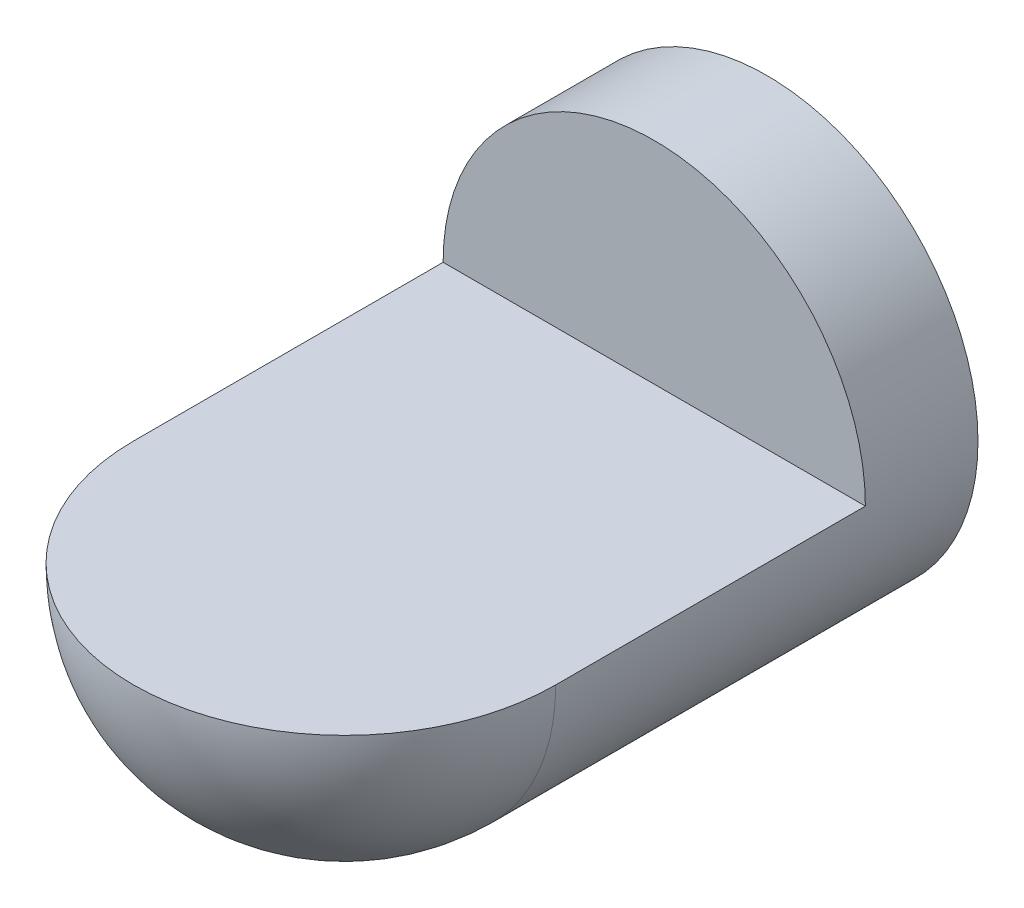
SolidWorks part; units mm, degrees
ref_plane "Front Plane" through (0, 0, 0) normal (0, 0, 1) x (1, 0, 0)
ref_plane "Top Plane" through (0, 0, 0) normal (0, 1, 0) x (1, 0, 0)
ref_plane "Right Plane" through (0, 0, 0) normal (1, 0, 0) x (0, 0, -1)
sketch "Sketch1" plane through (0, 0, 0) normal (1, 0, 0) x (0, 0, -1)
  line L0 (-146.9091, 0) -> (313.5945, 0) construction
  line L1 (150, 0) -> (-75, 0)
  line L2 (150, 0) -> (150, 75)
  line L3 (0, 75) -> (150, 75)
  arc A0 (-75, 0) -> (0, 75) centre (0, 0) cw
  dimension "D1" = 75
  dimension "D2" = 150
revolve "Revolve1" add sketch "Sketch1" angle 360 about L0
sketch "Sketch2" plane through (0, 0, 0) normal (1, 0, 0) x (0, 0, -1)
  line L0 (-88.0407, 0) -> (120.4455, 0) construction
  line L1 (110, 0) -> (110, 75)
  line L2 (150, 75) -> (0, 75) construction
  line L3 (110, 0) -> (-75, 0)
  line L4 (110, 75) -> (0, 75)
  line L5 (150, -75) -> (150, 75) construction
  arc A0 (0, 75) -> (0, -75) centre (0, 0) ccw construction
  arc A1 (-75, 0) -> (0, 75) centre (0, 0) cw
  dimension "D1" = 40
extrude "Cut-Extrude1" cut sketch "Sketch2" along normal through all and the other way through all
ref_axis "Axis1" through (0, 0, -161.25) along (0, 0, 1)
ref_axis "Axis2" through (0, 82.5, 0) along (0, -1, 0)
equation "\"base_link_length\"=150"
equation "\"link1_diameter\"=150"
equation "\"D1@Sketch1\"=\"link1_diameter\"/2"
equation "\"link1_length\"=150"
equation "\"D2@Sketch1\"=\"link1_length\""
equation "\"link2_diameter\"=150"
equation "\"link2_length\"=300"
equation "\"link3_diameter\"=150"
equation "\"link3_length\"=150"
equation "\"link4_diameter\"=150"
equation "\"link4_length\"=150"
equation "\"link5_diameter\"=150"
equation "\"link5_length\"=200"
equation "\"end_effector_diameter\"=150"
equation "\"end_effector_length\"=150"
equation "\"base_link_diameterA\"=200"
equation "\"base_link_diameterB\"=150"
equation "\"base_link_lengthA\"=50"
